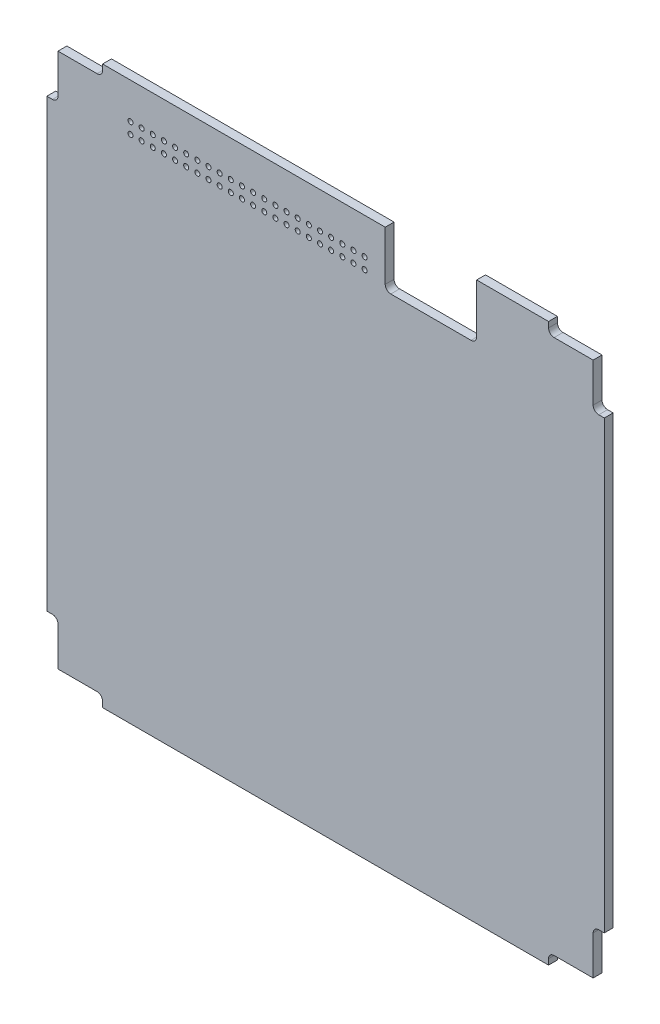
SolidWorks part; units mm, degrees
ref_plane "Front Plane" through (0, 0, 0) normal (0, 0, 1) x (1, 0, 0)
ref_plane "Top Plane" through (0, 0, 0) normal (0, 1, 0) x (1, 0, 0)
ref_plane "Right Plane" through (0, 0, 0) normal (1, 0, 0) x (0, 0, -1)
sketch "Sketch1" plane through (0, 0, 0) normal (0, 0, 1) x (1, 0, 0)
  line L0 (-40, 50) -> (-40, 48)
  line L1 (-50, -50) -> (50, -50)
  line L2 (-50, -50) -> (-50, 50)
  line L3 (-50, 50) -> (50, 50)
  line L4 (50, -50) -> (50, 50)
  line L5 (-50, -50) -> (50, 50) construction
  line L6 (-50, 50) -> (50, -50) construction
  line L7 (-50, 50) -> (-40, 50)
  line L8 (-50, 50) -> (-50, 40)
  line L9 (-40, 48) -> (-48, 48)
  line L10 (-48, 48) -> (-48, 40)
  line L11 (50, 50) -> (40, 50)
  line L12 (50, 50) -> (50, 40)
  line L13 (-48, 40) -> (-50, 40)
  line L14 (50, 40) -> (48, 40)
  line L15 (-50, -50) -> (-37.8649, -50)
  line L16 (-50, -50) -> (-50, -37.8649)
  line L17 (50, 50) -> (50, 40)
  line L18 (50, 50) -> (40, 50)
  line L19 (50, -50) -> (41.5, -50)
  line L20 (50, -50) -> (50, -41.5)
  line L21 (48, 40) -> (48, 48)
  line L22 (48, 48) -> (40, 48)
  line L23 (40, 48) -> (40, 50)
  line L24 (40, -50) -> (40, -48)
  line L25 (50, -50) -> (40, -50)
  line L26 (50, -50) -> (50, -40)
  line L27 (40, -48) -> (48, -48)
  line L28 (48, -48) -> (48, -40)
  line L29 (48, -40) -> (50, -40)
  line L30 (-50, -40) -> (-48, -40)
  line L31 (-50, -50) -> (-50, -40)
  line L32 (-50, -50) -> (-40, -50)
  line L33 (-48, -40) -> (-48, -48)
  line L34 (-48, -48) -> (-40, -48)
  line L35 (-40, -48) -> (-40, -50)
  point P0 (0, 0)
  point P38 (0, 0)
  dimension "D1" = 100
  dimension "D2" = 100
  dimension "D3" = 2
  dimension "D4" = 10
  dimension "D5" = 4
extrude "Boss-Extrude1" add sketch "Sketch1" along normal blind 1.5875 contours L1 L4 L3 L2 region at (0, 0, 0)
fillet "Fillet1" radius 1 8 edges at (-48, -40, 0.7937) (-40, -48, 0.7937) (40, -48, 0.7937) (48, -40, 0.7937) (48, 40, 0.7937) (40, 48, 0.7937) (-40, 48, 0.7937) (-48, 40, 0.7937)
sketch "Sketch2" plane through (0, 0, 1.5875) normal (0, 0, 1) x (1, 0, 0)
  line L0 (0, 50) -> (0, -50) construction
  line L1 (-40, 50) -> (40, 50) construction
  line L2 (-40, -50) -> (40, -50) construction
  line L4 (-36, 45.8) -> (8, 45.8) construction
  line L5 (-36, 45.8) -> (-36, 43.55) construction
  line L6 (-36, 43.55) -> (8, 43.55) construction
  line L7 (8, 45.8) -> (8, 43.55) construction
  line L8 (-36, 50) -> (8, 50) construction
  line L9 (-36, 50) -> (-36, 45.8) construction
  line L10 (-36, 45.8) -> (8, 45.8) construction
  line L11 (8, 50) -> (8, 45.8) construction
  circle A0 centre (-35, 43.55) radius 0.45
  circle A1 centre (-33, 43.55) radius 0.45
  circle A2 centre (-31, 43.55) radius 0.45
  circle A3 centre (-29, 43.55) radius 0.45
  circle A4 centre (-27, 43.55) radius 0.45
  circle A5 centre (-25, 43.55) radius 0.45
  circle A6 centre (-23, 43.55) radius 0.45
  circle A7 centre (-21, 43.55) radius 0.45
  circle A8 centre (-19, 43.55) radius 0.45
  circle A9 centre (-17, 43.55) radius 0.45
  circle A10 centre (-15, 43.55) radius 0.45
  circle A11 centre (-13, 43.55) radius 0.45
  circle A12 centre (-11, 43.55) radius 0.45
  circle A13 centre (-9, 43.55) radius 0.45
  circle A14 centre (-7, 43.55) radius 0.45
  circle A15 centre (-5, 43.55) radius 0.45
  circle A16 centre (-3, 43.55) radius 0.45
  circle A17 centre (-1, 43.55) radius 0.45
  circle A18 centre (1, 43.55) radius 0.45
  circle A19 centre (3, 43.55) radius 0.45
  circle A20 centre (5, 43.55) radius 0.45
  circle A21 centre (7, 43.55) radius 0.45
  circle A22 centre (-33, 41.55) radius 0.45
  circle A23 centre (-31, 41.55) radius 0.45
  circle A24 centre (-29, 41.55) radius 0.45
  circle A25 centre (-27, 41.55) radius 0.45
  circle A26 centre (-25, 41.55) radius 0.45
  circle A27 centre (-23, 41.55) radius 0.45
  circle A28 centre (-21, 41.55) radius 0.45
  circle A29 centre (-19, 41.55) radius 0.45
  circle A30 centre (-17, 41.55) radius 0.45
  circle A31 centre (-15, 41.55) radius 0.45
  circle A32 centre (-13, 41.55) radius 0.45
  circle A33 centre (-11, 41.55) radius 0.45
  circle A34 centre (-9, 41.55) radius 0.45
  circle A35 centre (-7, 41.55) radius 0.45
  circle A36 centre (-5, 41.55) radius 0.45
  circle A37 centre (-3, 41.55) radius 0.45
  circle A38 centre (-1, 41.55) radius 0.45
  circle A39 centre (1, 41.55) radius 0.45
  circle A40 centre (3, 41.55) radius 0.45
  circle A41 centre (5, 41.55) radius 0.45
  circle A42 centre (7, 41.55) radius 0.45
  circle A43 centre (-35, 41.55) radius 0.45
  dimension "D1" = 0.9
  dimension "D6" = 15
  dimension "D4" = 42
  dimension "D5" = 2
  dimension "D7" = 2.25
  dimension "D8" = 44
  dimension "D10" = 1
  dimension "D11" = 4.2
  dimension "D2" = 22
  dimension "D3" = 2
extrude "Cut-Extrude1" cut sketch "Sketch2" against normal through all
sketch "Sketch3" plane through (0, 50, 0) normal (0, 1, 0) x (1, 0, 0)
  line L0 (-40, 0) -> (40, 0) construction
  line L1 (10.7, 0) -> (19.7, 0)
  line L2 (10.7, 0) -> (10.7, -1.5875)
  line L3 (10.7, -1.5875) -> (19.7, -1.5875)
  line L5 (-40, -1.5875) -> (40, -1.5875) construction
  line L6 (15.2, 0) -> (15.2, -1.5875) construction
  line L7 (12, 0) -> (12, -1.5875) construction
  line L8 (18.4, 0) -> (18.4, -1.5875) construction
  line L9 (-40, -1.5875) -> (40, -1.5875) construction
  line L10 (7, 0) -> (7, -1.5875) construction
  line L11 (6.55, -1.5875) -> (7.45, -1.5875) construction
  line L12 (19.7, 0) -> (27.1, 0)
  line L14 (19.7, -1.5875) -> (27.1, -1.5875)
  line L15 (27.1, 0) -> (27.1, -1.5875)
  dimension "D1" = 9
  dimension "D2" = 6.4
  dimension "D3" = 3.2
  dimension "D4" = 5
  dimension "D5" = 7.4
extrude "Cut-Extrude2" cut sketch "Sketch3" against normal blind 9.8806
fillet "Fillet2" radius 1 2 edges at (10.7, 40.1194, 0.7938) (27.1, 40.1194, 0.7937)
